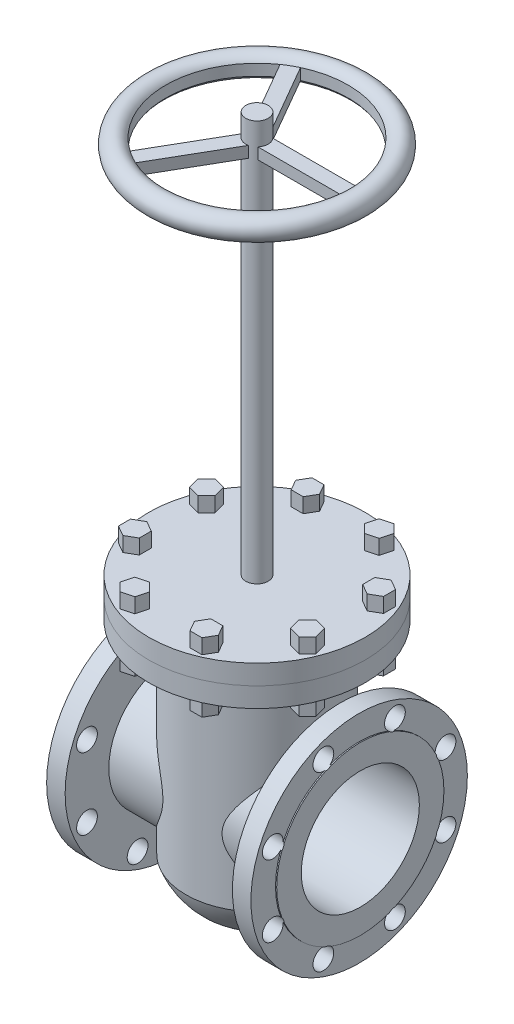
SolidWorks part; units mm, degrees
ref_plane "Front Plane" through (0, 0, 0) normal (0, 0, 1) x (1, 0, 0)
ref_plane "Top Plane" through (0, 0, 0) normal (0, 1, 0) x (1, 0, 0)
ref_plane "Right Plane" through (0, 0, 0) normal (1, 0, 0) x (0, 0, -1)
sketch "Weld End Sketch" plane through (0, 0, 0) normal (1, 0, 0) x (0, 0, -1)
  circle A0 centre (0, 0) radius 83.312
  dimension "d+2*t" = 166.624
extrude "Weld End" add sketch "Weld End Sketch" against normal mid plane 266.7
sketch "Flange Outlet Sketch" plane through (133.35, 0, 0) normal (1, 0, 0) x (0, 0, -1)
  circle A0 centre (0, 0) radius 139.7
  dimension "O" = 279.4
extrude "Flange Outlet" add sketch "Flange Outlet Sketch" against normal blind 25.4
sketch "Hub Cut Sketch" plane through (133.35, 0, 0) normal (1, 0, 0) x (0, 0, -1)
  circle A0 centre (0, 0) radius 107.95
  dimension "R" = 215.9
extrude "Hub Cut" cut sketch "Hub Cut Sketch" against normal blind 1.524 flip side to cut
sketch "Bolt Hole Sketch" plane through (133.35, 0, 0) normal (1, 0, 0) x (0, 0, -1)
  line L1 (0, 0) -> (0, 87.6028) construction
  line L2 (0, 0) -> (34.3727, 82.9831) construction
  circle A0 centre (0, 0) radius 120.65 construction
  circle A1 centre (46.1708, 111.4661) radius 13.4112
  dimension "DH*1.2" = 26.8224
  dimension "BC" = 241.3
  dimension "Angle" = 22.5
extrude "Bolt Hole" cut sketch "Bolt Hole Sketch" against normal up to surface (25.4 mm away) up to face at (107.95, 0, -83.312)
pattern_circular "Bolt Hole Pattern" count 8 every 45 about axis through (-133.35, 0, 0) along (1, 0, 0) of "Bolt Hole"
mirror "Flange Mirror" about plane through (0, 0, 0) normal (1, 0, 0) of "Hub Cut", "Flange Outlet", "Bolt Hole", "Bolt Hole Pattern"
sketch "Body Sketch" plane through (0, 0, 0) normal (0, 0, 1) x (1, 0, 0)
  line L0 (-91.6432, 177.8) -> (-91.6432, -83.312)
  line L1 (0, -199.4458) -> (0, 283.4066) construction
  line L2 (-107.95, -83.312) -> (107.95, -83.312) construction
  line L3 (-107.95, -83.312) -> (107.95, -83.312) construction
  line L5 (0, -148.082) -> (0, 177.8)
  line L6 (-91.6432, 177.8) -> (0, 177.8)
  arc A0 (-91.6432, -83.312) -> (0, -148.082) centre (0, -50.8639) ccw
  dimension "R*.3" = 64.77
  dimension "O/2+1.5* C1" = 177.8
  dimension "OD" = 183.2864
revolve "Body" add sketch "Body Sketch" angle 360 about L1
sketch "Flange Bottom Sketch" plane through (0, 177.8, 0) normal (0, 1, 0) x (-1, 0, 0)
  circle A0 centre (0, 0) radius 139.7
  dimension "O" = 279.4
extrude "Flange Bottom" add sketch "Flange Bottom Sketch" along normal blind 25.4
sketch "Flange Top Sketch" plane through (0, 203.2, 0) normal (0, 1, 0) x (-1, 0, 0)
  circle A1 centre (0, 0) radius 139.7
  circle A2 centre (0, 0) radius 139.7
  dimension "D1" = 0
extrude "Flange Top" add sketch "Flange Top Sketch" along normal blind 25.4
ref_plane "Driver Plane" through (0, 709.93, 0) normal (0, 1, 0) x (-1, 0, 0)
sketch "Driver Path" plane through (0, 709.93, 0) normal (0, 1, 0) x (-1, 0, 0)
  circle A0 centre (0, 0) radius 144.78
  dimension "D" = 289.56
sketch "Driver Profile" plane through (0, 0, 0) normal (0, 0, 1) x (1, 0, 0)
  line L0 (144.78, 709.93) -> (-144.78, 709.93) construction
  line L1 (-117.7637, 717.169) -> (0, 717.169)
  line L2 (144.78, 709.93) -> (-144.78, 709.93) construction
  line L3 (-117.7637, 702.691) -> (0, 702.691)
  line L4 (0, 717.169) -> (0, 702.691)
  arc A0 (-117.7637, 717.169) -> (-117.7637, 702.691) centre (-130.302, 709.93) ccw
  dimension "D1" = 14.478
  dimension "D/20" = 14.478
sweep "Driver Sweep" add profiles "Driver Profile" path "Driver Path"
sketch "Centre Support Sketch" plane through (0, 717.169, 0) normal (0, 1, 0) x (-1, 0, 0)
  circle A0 centre (0, 0) radius 14.478
  dimension "D/10" = 28.956
extrude "Centre Support" add sketch "Centre Support Sketch" against normal up to surface (488.569 mm away) and the other way blind 28.956 up to face at (0, 228.6, 139.7)
sketch "Driver Cut Sketch" plane through (0, 717.169, 0) normal (0, 1, 0) x (-1, 0, 0)
  line L0 (0, 0) -> (0, 113.8697) construction
  line L1 (0, 0) -> (-104.7757, 0) construction
  line L2 (50.3249, 106.4692) -> (-2.9632, 14.1715)
  line L3 (-117.3675, -9.652) -> (-10.7913, -9.652)
  line L4 (67.0426, 96.8172) -> (13.7545, 4.5195)
  line L5 (-117.3675, 9.652) -> (-10.7913, 9.652)
  line L6 (67.0426, -96.8172) -> (13.7545, -4.5195)
  line L7 (50.3249, -106.4692) -> (-2.9632, -14.1715)
  circle A0 centre (0, 0) radius 117.7637 construction
  arc A1 (50.3249, 106.4692) -> (-117.3675, 9.652) centre (0, 0) ccw
  circle A2 centre (0, 0) radius 14.478 construction
  arc A3 (-10.7913, -9.652) -> (-2.9632, -14.1715) centre (0, 0) ccw
  arc A4 (-2.9632, 14.1715) -> (-10.7913, 9.652) centre (0, 0) ccw
  arc A5 (13.7545, -4.5195) -> (13.7545, 4.5195) centre (0, 0) ccw
  arc A6 (67.0426, -96.8172) -> (67.0426, 96.8172) centre (0, 0) ccw
  arc A7 (-117.3675, -9.652) -> (50.3249, -106.4692) centre (0, 0) ccw
  dimension "D/30" = 9.652
extrude "Driver Cut" cut sketch "Driver Cut Sketch" against normal up to surface (14.478 mm away) up to face at (0, 702.691, 14.478)
ref_plane "Bolt Plane" through (0, 247.65, 0) normal (0, 1, 0) x (-1, 0, 0)
sketch "ID Cut Sketch" plane through (133.35, 0, 0) normal (1, 0, 0) x (0, 0, -1)
  circle A0 centre (0, 0) radius 76.2
  dimension "d" = 152.4
extrude "ID Cut" cut sketch "ID Cut Sketch" against normal through all
sketch "Bolt Sketch" plane through (0, 247.65, 0) normal (0, 1, 0) x (-1, 0, 0)
  line L0 (0, 0) -> (-127.3205, -52.7379) construction
  line L1 (0, 0) -> (-142.2485, 0) construction
  line L2 (-111.4661, -30.6848) -> (-124.8773, -38.4278)
  line L3 (-124.8773, -38.4278) -> (-124.8773, -53.9137)
  line L4 (-124.8773, -53.9137) -> (-111.4661, -61.6567)
  line L5 (-111.4661, -61.6567) -> (-98.0549, -53.9137)
  line L6 (-98.0549, -53.9137) -> (-98.0549, -38.4278)
  line L7 (-98.0549, -38.4278) -> (-111.4661, -30.6848)
  circle A0 centre (0, 0) radius 120.65 construction
  circle A2 centre (-111.4661, -46.1708) radius 13.4112 construction
  dimension "BC" = 241.3
  dimension "DH*1.2" = 26.8224
  dimension "Angle" = 22.5
extrude "Bolt" add sketch "Bolt Sketch" against normal blind 88.9
pattern_circular "Bolt Pattern" count 8 every 45 about axis through (0, 203.2, 0) along (0, -1, 0) of "Bolt"
sketch "Sketch1" plane through (0, 0, 0) normal (0, 0, 1) x (1, 0, 0)
  line L1 (139.7, 203.2) -> (-139.7, 203.2)
  line L2 (139.7, 203.2) -> (-139.7, 203.2)
  dimension "D1" = 0
split line "Split Line1"
sketch "CPointSketch" plane through (0, 0, 0) normal (0, 0, 1) x (1, 0, 0)
  line L0 (-133.35, 83.312) -> (-133.35, -83.312) construction
  line L1 (-133.35, 0) -> (133.35, 0) construction
  line L2 (133.35, -83.312) -> (133.35, 83.312) construction
  point P0 (-133.35, 0)
  point P1 (133.35, 0)
  point P8 (0, 0)
other "CPoint1" parameters "Diameter"=152.4, "StubLength"=0
ref_axis "Axis1" through (-143.35, 0, 0) along (1, 0, 0)
other "CPoint2" parameters "Diameter"=152.4, "StubLength"=0
ref_axis "Axis2" through (143.35, 0, 0) along (-1, 0, 0)
other "RPoint1"
equation "\"D1@Driver Profile\" = \"D/20@Driver Profile\""
equation "\"D2@Centre Support\" = \"D/10@Centre Support Sketch\""
